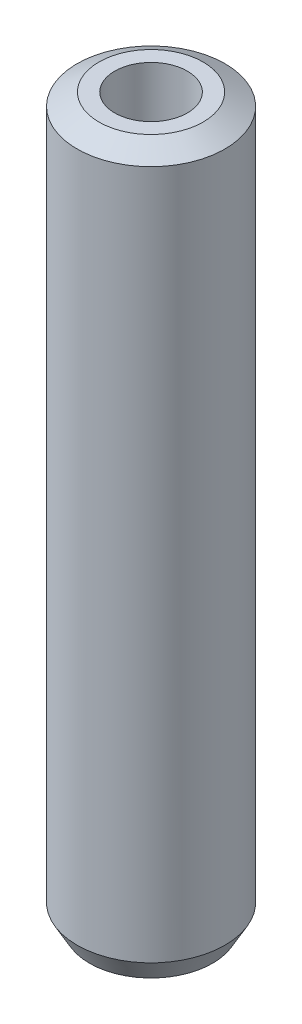
SolidWorks part; units mm, degrees
ref_plane "Front Plane" through (0, 0, 0) normal (0, 0, 1) x (1, 0, 0)
ref_plane "Top Plane" through (0, 0, 0) normal (0, 1, 0) x (1, 0, 0)
ref_plane "Right Plane" through (0, 0, 0) normal (1, 0, 0) x (0, 0, -1)
sketch "Sketch1" plane through (0, 0, 0) normal (0, 1, 0) x (1, 0, 0)
  circle A0 centre (0, 0) radius 7.5
  dimension "SHAFT_OD" = 15
extrude "Boss-Extrude1" add sketch "Sketch1" along normal blind 73.4034
sketch "Sketch2" plane through (0, 0, 0) normal (0, 1, 0) x (1, 0, 0)
  circle A0 centre (0, 0) radius 3.6813
  dimension "BORE_D" = 7.3626
extrude "Cut-Extrude1" cut sketch "Sketch2" along normal through all
chamfer "Chamfer1" distance 1.2548 angle 60.513 2 edges at (0, 73.4034, 7.5) (0, 0, 7.5) first distance on face at (0, 73.4034, 7.5) first distance on face at (0, 0, 3.6813)
